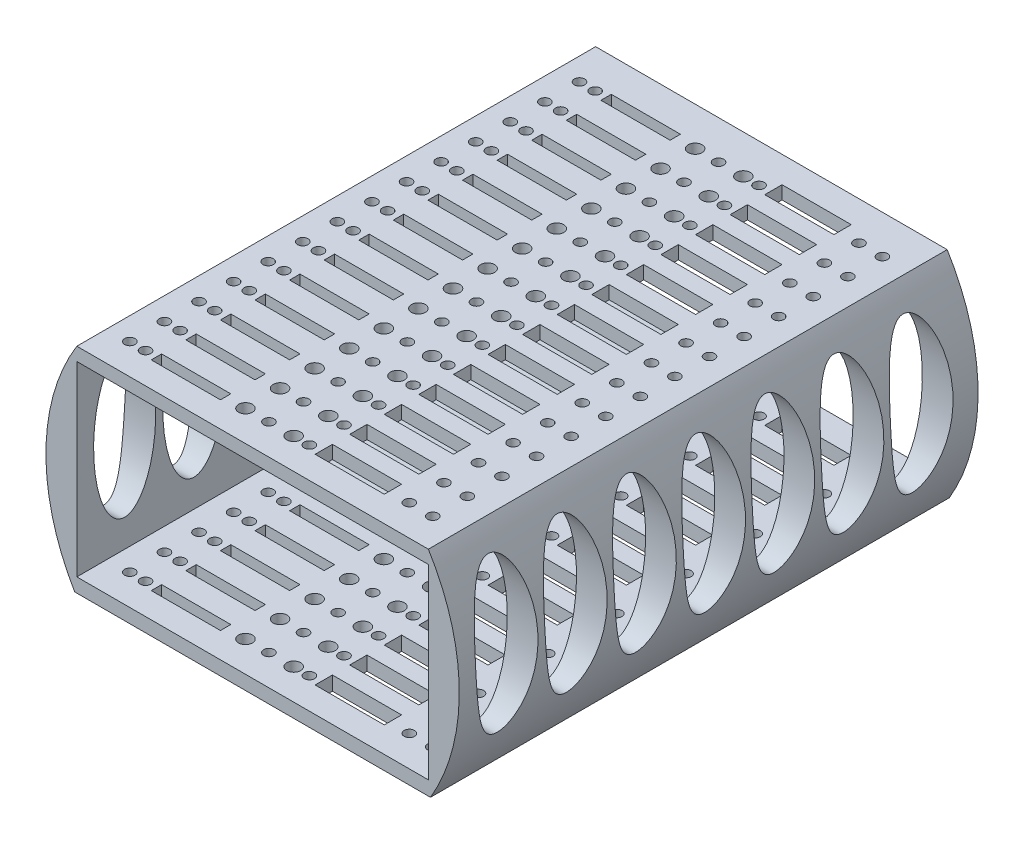
SolidWorks part; units mm, degrees
ref_plane "前视基准面" through (0, 0, 0) normal (0, 0, 1) x (1, 0, 0)
ref_plane "上视基准面" through (0, 0, 0) normal (0, 1, 0) x (1, 0, 0)
ref_plane "右视基准面" through (0, 0, 0) normal (1, 0, 0) x (0, 0, -1)
sketch "草图4" plane through (0, 0, 0) normal (0, 0, 1) x (1, 0, 0)
  circle A0 centre (0, 0) radius 59.75
  dimension "D1" = 119.5
extrude "凸台-拉伸1" add sketch "草图4" along normal blind 150
sketch "草图5" plane through (0, 0, 150) normal (0, 0, 1) x (1, 0, 0)
  line L1 (-51.4335, -30.4082) -> (51.4335, -30.4082)
  line L3 (-51.4335, -119.9668) -> (51.4335, -119.9668)
  line L5 (-94.8289, 51.0695) -> (94.5921, 51.0695)
  line L6 (-94.8289, 51.0695) -> (-94.8289, -47.7322)
  line L7 (-94.8289, -47.7322) -> (94.5921, -47.7322)
  line L8 (94.5921, 51.0695) -> (94.5921, -47.7322)
  line L9 (-50.8181, 31.4258) -> (50.8181, 31.4258)
  line L11 (-50.8181, 120) -> (50.8181, 120)
  line L13 (-50.8181, 27.5996) -> (50.8181, 27.5996)
  line L14 (-50.8181, 27.5996) -> (-50.8181, -26.3366)
  line L15 (-50.8181, -26.3366) -> (50.8181, -26.3366)
  line L16 (50.8181, 27.5996) -> (50.8181, -26.3366)
  circle A0 centre (0, 0) radius 59.75 construction
  arc A1 (-50.8181, 31.4258) -> (50.8181, 31.4258) centre (0, 0) ccw
  arc A2 (-51.4335, -30.4082) -> (51.4335, -30.4082) centre (0, 0) ccw
  arc A3 (50.8181, 31.4258) -> (-50.8181, 31.4258) centre (0, 0) ccw
  arc A4 (-51.4335, -30.4082) -> (51.4335, -30.4082) centre (0, 0) ccw
  circle M13 centre (0, 0) radius 59.75
extrude "切除-拉伸3" cut sketch "草图5" against normal through all and the other way through all contours L9 L5 M13 | L5 M13 region at (0, 40.5019, 150) region at (0, 54.5643, 150)
extrude "切除-拉伸4" cut sketch "草图5<3>" against normal through all contours L7 L1 M13 | L7 M13 region at (0, -38.5769, 150) region at (0, -52.5833, 150)
sketch "草图5<3>" plane through (0, 0, 150) normal (0, 0, 1) x (1, 0, 0) same geometry as "草图5"
extrude "切除-拉伸5" cut sketch "草图5<4>" against normal blind 150 contours L16 L13 L14 L15 region at (0, 0.6315, 150)
sketch "草图5<4>" plane through (0, 0, 150) normal (0, 0, 1) x (1, 0, 0) same geometry as "草图5"
sketch "草图6" plane through (50.8181, 0, 0) normal (-1, 0, 0) x (0, 0, 1)
  ellipse E0 centre (16.1642, 3.3949) end of major axis (16.1642, -18.3032) minor radius 8.9849
  ellipse E1 centre (36.1642, 3.3949) end of major axis (36.1642, -18.3032) minor radius 8.9849
  ellipse E2 centre (56.1642, 3.3949) end of major axis (56.1642, -18.3032) minor radius 8.9849
  ellipse E3 centre (76.1642, 3.3949) end of major axis (76.1642, -18.3032) minor radius 8.9849
  ellipse E4 centre (96.1642, 3.3949) end of major axis (96.1642, -18.3032) minor radius 8.9849
  ellipse E5 centre (116.1642, 3.3949) end of major axis (116.1642, -18.3032) minor radius 8.9849
  ellipse E6 centre (136.1642, 3.3949) end of major axis (136.1642, -18.3032) minor radius 8.9849
extrude "切除-拉伸6" cut sketch "草图6" against normal through all both and the other way through all
sketch "草图8" plane through (0, 31.4258, 0) normal (0, 1, 0) x (1, 0, 0)
  line L1 (-36.6301, -9.6685) -> (-16.6301, -9.6685)
  line L2 (-36.6301, -9.6685) -> (-36.6301, -12.6685)
  line L3 (-36.6301, -12.6685) -> (-16.6301, -12.6685)
  line L4 (-16.6301, -9.6685) -> (-16.6301, -12.6685)
  line L8 (10.6924, -7.6176) -> (30.6924, -7.6176)
  line L9 (10.6924, -7.6176) -> (10.6924, -12.6176)
  line L10 (10.6924, -12.6176) -> (30.6924, -12.6176)
  line L11 (30.6924, -7.6176) -> (30.6924, -12.6176)
  line L12 (-36.6301, -19.6685) -> (-16.6301, -19.6685)
  line L13 (-36.6301, -19.6685) -> (-36.6301, -22.6685)
  line L14 (-36.6301, -22.6685) -> (-16.6301, -22.6685)
  line L15 (-16.6301, -19.6685) -> (-16.6301, -22.6685)
  line L16 (10.6924, -17.6176) -> (30.6924, -17.6176)
  line L17 (10.6924, -17.6176) -> (10.6924, -22.6176)
  line L18 (10.6924, -22.6176) -> (30.6924, -22.6176)
  line L19 (30.6924, -17.6176) -> (30.6924, -22.6176)
  line L20 (-36.6301, -29.6685) -> (-16.6301, -29.6685)
  line L21 (-36.6301, -29.6685) -> (-36.6301, -32.6685)
  line L22 (-36.6301, -32.6685) -> (-16.6301, -32.6685)
  line L23 (-16.6301, -29.6685) -> (-16.6301, -32.6685)
  line L24 (10.6924, -27.6176) -> (30.6924, -27.6176)
  line L25 (10.6924, -27.6176) -> (10.6924, -32.6176)
  line L26 (10.6924, -32.6176) -> (30.6924, -32.6176)
  line L27 (30.6924, -27.6176) -> (30.6924, -32.6176)
  line L28 (-36.6301, -39.6685) -> (-16.6301, -39.6685)
  line L29 (-36.6301, -39.6685) -> (-36.6301, -42.6685)
  line L30 (-36.6301, -42.6685) -> (-16.6301, -42.6685)
  line L31 (-16.6301, -39.6685) -> (-16.6301, -42.6685)
  line L32 (10.6924, -37.6176) -> (30.6924, -37.6176)
  line L33 (10.6924, -37.6176) -> (10.6924, -42.6176)
  line L34 (10.6924, -42.6176) -> (30.6924, -42.6176)
  line L35 (30.6924, -37.6176) -> (30.6924, -42.6176)
  line L36 (-36.6301, -49.6685) -> (-16.6301, -49.6685)
  line L37 (-36.6301, -49.6685) -> (-36.6301, -52.6685)
  line L38 (-36.6301, -52.6685) -> (-16.6301, -52.6685)
  line L39 (-16.6301, -49.6685) -> (-16.6301, -52.6685)
  line L40 (10.6924, -47.6176) -> (30.6924, -47.6176)
  line L41 (10.6924, -47.6176) -> (10.6924, -52.6176)
  line L42 (10.6924, -52.6176) -> (30.6924, -52.6176)
  line L43 (30.6924, -47.6176) -> (30.6924, -52.6176)
  line L44 (-36.6301, -59.6685) -> (-16.6301, -59.6685)
  line L45 (-36.6301, -59.6685) -> (-36.6301, -62.6685)
  line L46 (-36.6301, -62.6685) -> (-16.6301, -62.6685)
  line L47 (-16.6301, -59.6685) -> (-16.6301, -62.6685)
  line L48 (10.6924, -57.6176) -> (30.6924, -57.6176)
  line L49 (10.6924, -57.6176) -> (10.6924, -62.6176)
  line L50 (10.6924, -62.6176) -> (30.6924, -62.6176)
  line L51 (30.6924, -57.6176) -> (30.6924, -62.6176)
  line L52 (-36.6301, -69.6685) -> (-16.6301, -69.6685)
  line L53 (-36.6301, -69.6685) -> (-36.6301, -72.6685)
  line L54 (-36.6301, -72.6685) -> (-16.6301, -72.6685)
  line L55 (-16.6301, -69.6685) -> (-16.6301, -72.6685)
  line L56 (10.6924, -67.6176) -> (30.6924, -67.6176)
  line L57 (10.6924, -67.6176) -> (10.6924, -72.6176)
  line L58 (10.6924, -72.6176) -> (30.6924, -72.6176)
  line L59 (30.6924, -67.6176) -> (30.6924, -72.6176)
  line L60 (-36.6301, -79.6685) -> (-16.6301, -79.6685)
  line L61 (-36.6301, -79.6685) -> (-36.6301, -82.6685)
  line L62 (-36.6301, -82.6685) -> (-16.6301, -82.6685)
  line L63 (-16.6301, -79.6685) -> (-16.6301, -82.6685)
  line L64 (10.6924, -77.6176) -> (30.6924, -77.6176)
  line L65 (10.6924, -77.6176) -> (10.6924, -82.6176)
  line L66 (10.6924, -82.6176) -> (30.6924, -82.6176)
  line L67 (30.6924, -77.6176) -> (30.6924, -82.6176)
  line L68 (-36.6301, -89.6685) -> (-16.6301, -89.6685)
  line L69 (-36.6301, -89.6685) -> (-36.6301, -92.6685)
  line L70 (-36.6301, -92.6685) -> (-16.6301, -92.6685)
  line L71 (-16.6301, -89.6685) -> (-16.6301, -92.6685)
  line L72 (10.6924, -87.6176) -> (30.6924, -87.6176)
  line L73 (10.6924, -87.6176) -> (10.6924, -92.6176)
  line L74 (10.6924, -92.6176) -> (30.6924, -92.6176)
  line L75 (30.6924, -87.6176) -> (30.6924, -92.6176)
  line L76 (-36.6301, -99.6685) -> (-16.6301, -99.6685)
  line L77 (-36.6301, -99.6685) -> (-36.6301, -102.6685)
  line L78 (-36.6301, -102.6685) -> (-16.6301, -102.6685)
  line L79 (-16.6301, -99.6685) -> (-16.6301, -102.6685)
  line L80 (10.6924, -97.6176) -> (30.6924, -97.6176)
  line L81 (10.6924, -97.6176) -> (10.6924, -102.6176)
  line L82 (10.6924, -102.6176) -> (30.6924, -102.6176)
  line L83 (30.6924, -97.6176) -> (30.6924, -102.6176)
  line L84 (-36.6301, -109.6685) -> (-16.6301, -109.6685)
  line L85 (-36.6301, -109.6685) -> (-36.6301, -112.6685)
  line L86 (-36.6301, -112.6685) -> (-16.6301, -112.6685)
  line L87 (-16.6301, -109.6685) -> (-16.6301, -112.6685)
  line L88 (10.6924, -107.6176) -> (30.6924, -107.6176)
  line L89 (10.6924, -107.6176) -> (10.6924, -112.6176)
  line L90 (10.6924, -112.6176) -> (30.6924, -112.6176)
  line L91 (30.6924, -107.6176) -> (30.6924, -112.6176)
  line L92 (-36.6301, -119.6685) -> (-16.6301, -119.6685)
  line L93 (-36.6301, -119.6685) -> (-36.6301, -122.6685)
  line L94 (-36.6301, -122.6685) -> (-16.6301, -122.6685)
  line L95 (-16.6301, -119.6685) -> (-16.6301, -122.6685)
  line L96 (10.6924, -117.6176) -> (30.6924, -117.6176)
  line L97 (10.6924, -117.6176) -> (10.6924, -122.6176)
  line L98 (10.6924, -122.6176) -> (30.6924, -122.6176)
  line L99 (30.6924, -117.6176) -> (30.6924, -122.6176)
  line L100 (-36.6301, -129.6685) -> (-16.6301, -129.6685)
  line L101 (-36.6301, -129.6685) -> (-36.6301, -132.6685)
  line L102 (-36.6301, -132.6685) -> (-16.6301, -132.6685)
  line L103 (-16.6301, -129.6685) -> (-16.6301, -132.6685)
  line L104 (10.6924, -127.6176) -> (30.6924, -127.6176)
  line L105 (10.6924, -127.6176) -> (10.6924, -132.6176)
  line L106 (10.6924, -132.6176) -> (30.6924, -132.6176)
  line L107 (30.6924, -127.6176) -> (30.6924, -132.6176)
  line L108 (-36.6301, -139.6685) -> (-16.6301, -139.6685)
  line L109 (-36.6301, -139.6685) -> (-36.6301, -142.6685)
  line L110 (-36.6301, -142.6685) -> (-16.6301, -142.6685)
  line L111 (-16.6301, -139.6685) -> (-16.6301, -142.6685)
  line L112 (10.6924, -137.6176) -> (30.6924, -137.6176)
  line L113 (10.6924, -137.6176) -> (10.6924, -142.6176)
  line L114 (10.6924, -142.6176) -> (30.6924, -142.6176)
  line L115 (30.6924, -137.6176) -> (30.6924, -142.6176)
  circle A0 centre (-44.3203, -11.1685) radius 1.5
  circle A1 centre (-39.7844, -11.1685) radius 1.5
  circle A2 centre (-10.8892, -11.1685) radius 2
  circle A3 centre (-4.107, -11.1685) radius 1.5
  circle A10 centre (3.0022, -11.1176) radius 2
  circle A11 centre (7.5381, -11.1176) radius 1.5
  circle A12 centre (36.4333, -11.1176) radius 1.5
  circle A13 centre (43.2155, -11.1176) radius 1.5
  circle A14 centre (-44.3203, -21.1685) radius 1.5
  circle A15 centre (-39.7844, -21.1685) radius 1.5
  circle A16 centre (-10.8892, -21.1685) radius 2
  circle A17 centre (-4.107, -21.1685) radius 1.5
  circle A18 centre (3.0022, -21.1176) radius 2
  circle A19 centre (7.5381, -21.1176) radius 1.5
  circle A20 centre (36.4333, -21.1176) radius 1.5
  circle A21 centre (43.2155, -21.1176) radius 1.5
  circle A22 centre (-44.3203, -31.1685) radius 1.5
  circle A23 centre (-39.7844, -31.1685) radius 1.5
  circle A24 centre (-10.8892, -31.1685) radius 2
  circle A25 centre (-4.107, -31.1685) radius 1.5
  circle A26 centre (3.0022, -31.1176) radius 2
  circle A27 centre (7.5381, -31.1176) radius 1.5
  circle A28 centre (36.4333, -31.1176) radius 1.5
  circle A29 centre (43.2155, -31.1176) radius 1.5
  circle A30 centre (-44.3203, -41.1685) radius 1.5
  circle A31 centre (-39.7844, -41.1685) radius 1.5
  circle A32 centre (-10.8892, -41.1685) radius 2
  circle A33 centre (-4.107, -41.1685) radius 1.5
  circle A34 centre (3.0022, -41.1176) radius 2
  circle A35 centre (7.5381, -41.1176) radius 1.5
  circle A36 centre (36.4333, -41.1176) radius 1.5
  circle A37 centre (43.2155, -41.1176) radius 1.5
  circle A38 centre (-44.3203, -51.1685) radius 1.5
  circle A39 centre (-39.7844, -51.1685) radius 1.5
  circle A40 centre (-10.8892, -51.1685) radius 2
  circle A41 centre (-4.107, -51.1685) radius 1.5
  circle A42 centre (3.0022, -51.1176) radius 2
  circle A43 centre (7.5381, -51.1176) radius 1.5
  circle A44 centre (36.4333, -51.1176) radius 1.5
  circle A45 centre (43.2155, -51.1176) radius 1.5
  circle A46 centre (-44.3203, -61.1685) radius 1.5
  circle A47 centre (-39.7844, -61.1685) radius 1.5
  circle A48 centre (-10.8892, -61.1685) radius 2
  circle A49 centre (-4.107, -61.1685) radius 1.5
  circle A50 centre (3.0022, -61.1176) radius 2
  circle A51 centre (7.5381, -61.1176) radius 1.5
  circle A52 centre (36.4333, -61.1176) radius 1.5
  circle A53 centre (43.2155, -61.1176) radius 1.5
  circle A54 centre (-44.3203, -71.1685) radius 1.5
  circle A55 centre (-39.7844, -71.1685) radius 1.5
  circle A56 centre (-10.8892, -71.1685) radius 2
  circle A57 centre (-4.107, -71.1685) radius 1.5
  circle A58 centre (3.0022, -71.1176) radius 2
  circle A59 centre (7.5381, -71.1176) radius 1.5
  circle A60 centre (36.4333, -71.1176) radius 1.5
  circle A61 centre (43.2155, -71.1176) radius 1.5
  circle A62 centre (-44.3203, -81.1685) radius 1.5
  circle A63 centre (-39.7844, -81.1685) radius 1.5
  circle A64 centre (-10.8892, -81.1685) radius 2
  circle A65 centre (-4.107, -81.1685) radius 1.5
  circle A66 centre (3.0022, -81.1176) radius 2
  circle A67 centre (7.5381, -81.1176) radius 1.5
  circle A68 centre (36.4333, -81.1176) radius 1.5
  circle A69 centre (43.2155, -81.1176) radius 1.5
  circle A70 centre (-44.3203, -91.1685) radius 1.5
  circle A71 centre (-39.7844, -91.1685) radius 1.5
  circle A72 centre (-10.8892, -91.1685) radius 2
  circle A73 centre (-4.107, -91.1685) radius 1.5
  circle A74 centre (3.0022, -91.1176) radius 2
  circle A75 centre (7.5381, -91.1176) radius 1.5
  circle A76 centre (36.4333, -91.1176) radius 1.5
  circle A77 centre (43.2155, -91.1176) radius 1.5
  circle A78 centre (-44.3203, -101.1685) radius 1.5
  circle A79 centre (-39.7844, -101.1685) radius 1.5
  circle A80 centre (-10.8892, -101.1685) radius 2
  circle A81 centre (-4.107, -101.1685) radius 1.5
  circle A82 centre (3.0022, -101.1176) radius 2
  circle A83 centre (7.5381, -101.1176) radius 1.5
  circle A84 centre (36.4333, -101.1176) radius 1.5
  circle A85 centre (43.2155, -101.1176) radius 1.5
  circle A86 centre (-44.3203, -111.1685) radius 1.5
  circle A87 centre (-39.7844, -111.1685) radius 1.5
  circle A88 centre (-10.8892, -111.1685) radius 2
  circle A89 centre (-4.107, -111.1685) radius 1.5
  circle A90 centre (3.0022, -111.1176) radius 2
  circle A91 centre (7.5381, -111.1176) radius 1.5
  circle A92 centre (36.4333, -111.1176) radius 1.5
  circle A93 centre (43.2155, -111.1176) radius 1.5
  circle A94 centre (-44.3203, -121.1685) radius 1.5
  circle A95 centre (-39.7844, -121.1685) radius 1.5
  circle A96 centre (-10.8892, -121.1685) radius 2
  circle A97 centre (-4.107, -121.1685) radius 1.5
  circle A98 centre (3.0022, -121.1176) radius 2
  circle A99 centre (7.5381, -121.1176) radius 1.5
  circle A100 centre (36.4333, -121.1176) radius 1.5
  circle A101 centre (43.2155, -121.1176) radius 1.5
  circle A102 centre (-44.3203, -131.1685) radius 1.5
  circle A103 centre (-39.7844, -131.1685) radius 1.5
  circle A104 centre (-10.8892, -131.1685) radius 2
  circle A105 centre (-4.107, -131.1685) radius 1.5
  circle A106 centre (3.0022, -131.1176) radius 2
  circle A107 centre (7.5381, -131.1176) radius 1.5
  circle A108 centre (36.4333, -131.1176) radius 1.5
  circle A109 centre (43.2155, -131.1176) radius 1.5
  circle A110 centre (-44.3203, -141.1685) radius 1.5
  circle A111 centre (-39.7844, -141.1685) radius 1.5
  circle A112 centre (-10.8892, -141.1685) radius 2
  circle A113 centre (-4.107, -141.1685) radius 1.5
  circle A114 centre (3.0022, -141.1176) radius 2
  circle A115 centre (7.5381, -141.1176) radius 1.5
  circle A116 centre (36.4333, -141.1176) radius 1.5
  circle A117 centre (43.2155, -141.1176) radius 1.5
  dimension "D3" = 5
  dimension "D4" = 3
  dimension "D5" = 3
  dimension "D1" = 3
  dimension "D2" = 20
  dimension "D6" = 14
extrude "切除-拉伸7" cut sketch "草图8" against normal through all both and the other way through all
